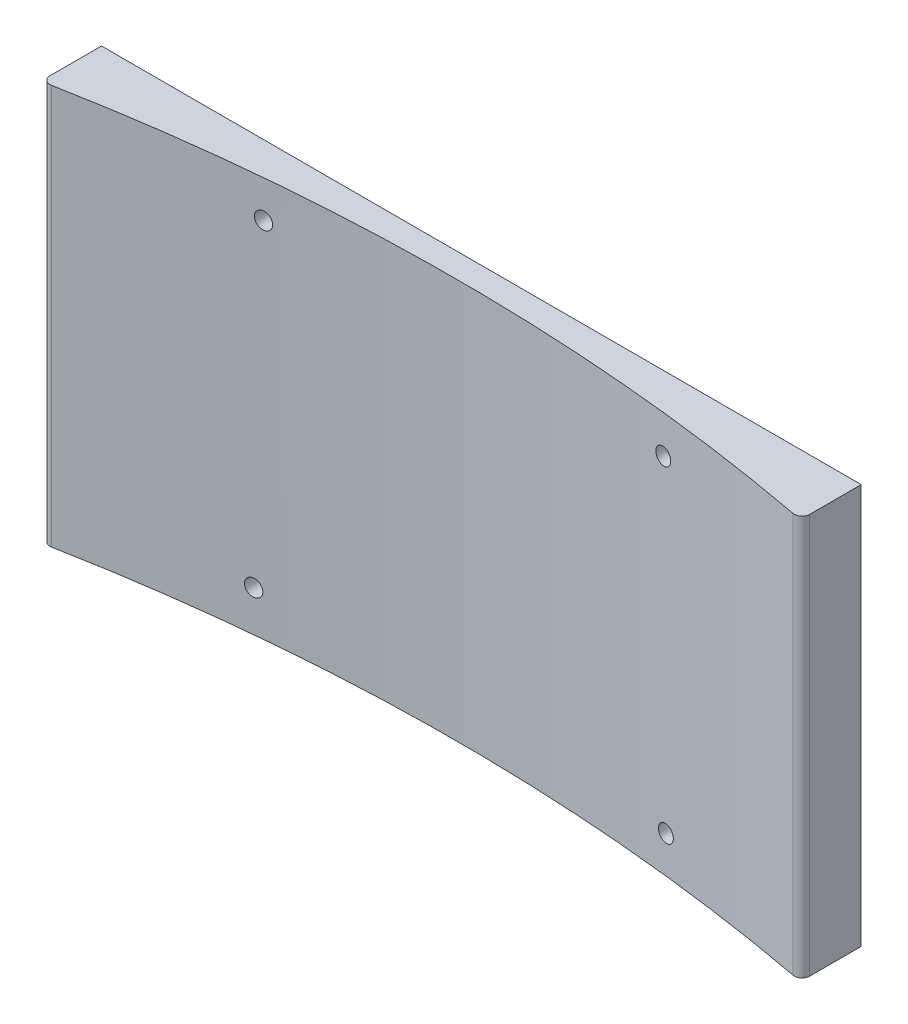
SolidWorks part; units mm, degrees
ref_plane "Front Plane" through (0, 0, 0) normal (0, 0, 1) x (1, 0, 0)
ref_plane "Top Plane" through (0, 0, 0) normal (0, 1, 0) x (1, 0, 0)
ref_plane "Right Plane" through (0, 0, 0) normal (1, 0, 0) x (0, 0, -1)
sketch "Sketch2" plane through (0, 0, 0) normal (0, 0, 1) x (1, 0, 0)
  line L0 (-121.572, 80.424) -> (-41.572, 80.424)
  line L1 (-41.572, 80.424) -> (-41.572, 27.78)
  line L2 (-41.572, 27.78) -> (-141.572, 27.78)
  line L3 (-141.572, 27.78) -> (-141.572, 80.424)
  line L4 (-141.572, 80.424) -> (-121.572, 80.424)
extrude "Boss-Extrude1" add sketch "Sketch2" along normal blind 2 from offset 20
sketch "Sketch3" plane through (0, 80.424, 0) normal (0, 1, 0) x (1, 0, 0)
  line L0 (-41.572, -22) -> (-41.572, -28)
  line L1 (-141.572, -22) -> (-141.572, -28)
  line L2 (-41.572, -22) -> (-141.572, -22)
  arc A0 (-41.572, -28) -> (-141.6974, -28.0243) centre (-91.572, -286.7643) ccw
  arc A1 (-91.6359, -38.2042) -> (-91.572, -38.1404) centre (-91.572, -38.2042) ccw
  line M3 (-141.572, -22) -> (-41.572, -22)
  dimension "D1" = 6
  dimension "D2" = 6
extrude "Boss-Extrude2" add sketch "Sketch3" against normal blind 52.64 contours A0 L0 L1 M3 region at (-42.5738, 80.424, 25)
sketch "Sketch5" plane through (0, 0, 20) normal (0, 0, -1) x (-1, 0, 0)
  circle A0 centre (115.905, 75.538) radius 1.1 construction
  circle A1 centre (117.094, 33.147) radius 1.1 construction
  circle A2 centre (62.836, 75.44) radius 1.1 construction
  circle A3 centre (62.455, 32.641) radius 1.1 construction
  circle A4 centre (115.905, 75.538) radius 1.1
  circle A5 centre (117.094, 33.147) radius 1.1
  circle A6 centre (62.836, 75.44) radius 1.1
  circle A7 centre (62.455, 32.641) radius 1.1
  circle A8 centre (62.455, 32.641) radius 1.1
  circle A9 centre (117.094, 33.147) radius 1.1
  circle A10 centre (115.905, 75.538) radius 1.1
  circle A11 centre (62.836, 75.44) radius 1.1
extrude "Cut-Extrude2" cut sketch "Sketch5" against normal blind 19.64 contours A7
extrude "Cut-Extrude3" cut sketch "Sketch5<5>" against normal blind 19.64 contours A6
sketch "Sketch5<5>" plane through (0, 0, 20) normal (0, 0, -1) x (-1, 0, 0) same geometry as "Sketch5"
extrude "Cut-Extrude4" cut sketch "Sketch5<6>" against normal blind 19.64 contours A4
sketch "Sketch5<6>" plane through (0, 0, 20) normal (0, 0, -1) x (-1, 0, 0) same geometry as "Sketch5"
extrude "Cut-Extrude5" cut sketch "Sketch5<7>" against normal blind 19.64 contours A5
sketch "Sketch5<7>" plane through (0, 0, 20) normal (0, 0, -1) x (-1, 0, 0) same geometry as "Sketch5"
fillet "Fillet1" radius 1 1 edges at (-41.572, 54.104, 28)
fillet "Fillet2" radius 1 1 edges at (-141.572, 54.104, 28)
